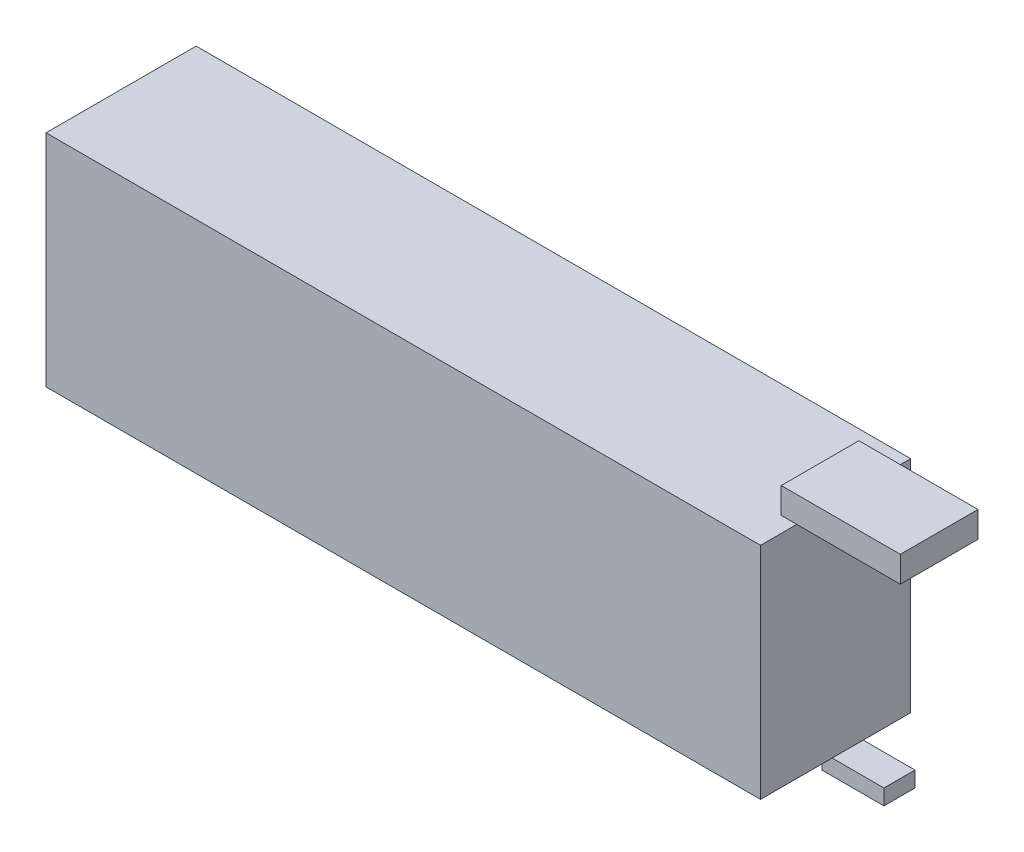
SolidWorks part; units mm, degrees
ref_plane "Front Plane" through (0, 0, 0) normal (0, 0, 1) x (1, 0, 0)
ref_plane "Top Plane" through (0, 0, 0) normal (0, 1, 0) x (1, 0, 0)
ref_plane "Right Plane" through (0, 0, 0) normal (1, 0, 0) x (0, 0, -1)
sketch "Sketch1" plane through (0, 0, 0) normal (0, 0, 1) x (1, 0, 0)
  line L1 (-69, 21.25) -> (69, 21.25)
  line L2 (-69, 21.25) -> (-69, -21.25)
  line L3 (-69, -21.25) -> (69, -21.25)
  line L4 (69, 21.25) -> (69, -21.25)
  line L5 (-69, 21.25) -> (69, -21.25) construction
  line L6 (-69, -21.25) -> (69, 21.25) construction
  point P0 (0, 0)
  dimension "D1" = 42.5
  dimension "D2" = 138
extrude "Boss-Extrude1" add sketch "Sketch1" along normal mid plane 29
sketch "Sketch2" plane through (0, 0, 0) normal (1, 0, 0) x (0, 0, -1)
  line L0 (-14.5, 21.25) -> (14.5, 21.25) construction
  line L1 (-7.5, 21.25) -> (7.5, 21.25)
  line L2 (-7.5, 21.25) -> (-7.5, 26.25)
  line L3 (-7.5, 26.25) -> (7.5, 26.25)
  line L4 (7.5, 21.25) -> (7.5, 26.25)
  line L5 (-7.5, 21.25) -> (7.5, 26.25) construction
  line L6 (-7.5, 26.25) -> (7.5, 21.25) construction
  line L7 (-0.6659, -21.25) -> (5.3341, -21.25)
  line L8 (-0.6659, -21.25) -> (-0.6659, -24.25)
  line L9 (-0.6659, -24.25) -> (5.3341, -24.25)
  line L10 (5.3341, -21.25) -> (5.3341, -24.25)
  line L11 (-0.6659, -21.25) -> (5.3341, -24.25) construction
  line L12 (-0.6659, -24.25) -> (5.3341, -21.25) construction
  line L13 (-14.5, -21.25) -> (14.5, -21.25) construction
  point P0 (0, 23.75)
  point P5 (2.3341, -22.75)
  dimension "D1" = 15
  dimension "D2" = 5
  dimension "D3" = 3
  dimension "D4" = 6
  dimension "D5" = 3
extrude "Boss-Extrude2" add sketch "Sketch2" along normal blind 20 and the other way blind 3 from surface contours L1 L4 L3 L2 region at (0, 23.75, 0) starting at face at (69, 0, 0)
extrude "Boss-Extrude3" add sketch "Sketch2<3>" along normal blind 10 and the other way blind 2 from surface contours L10 L7 L8 L9 region at (0, -22.75, -2.3341) starting at face at (69, 7.0833, 0)
sketch "Sketch2<3>" plane through (0, 0, 0) normal (1, 0, 0) x (0, 0, -1) same geometry as "Sketch2"
